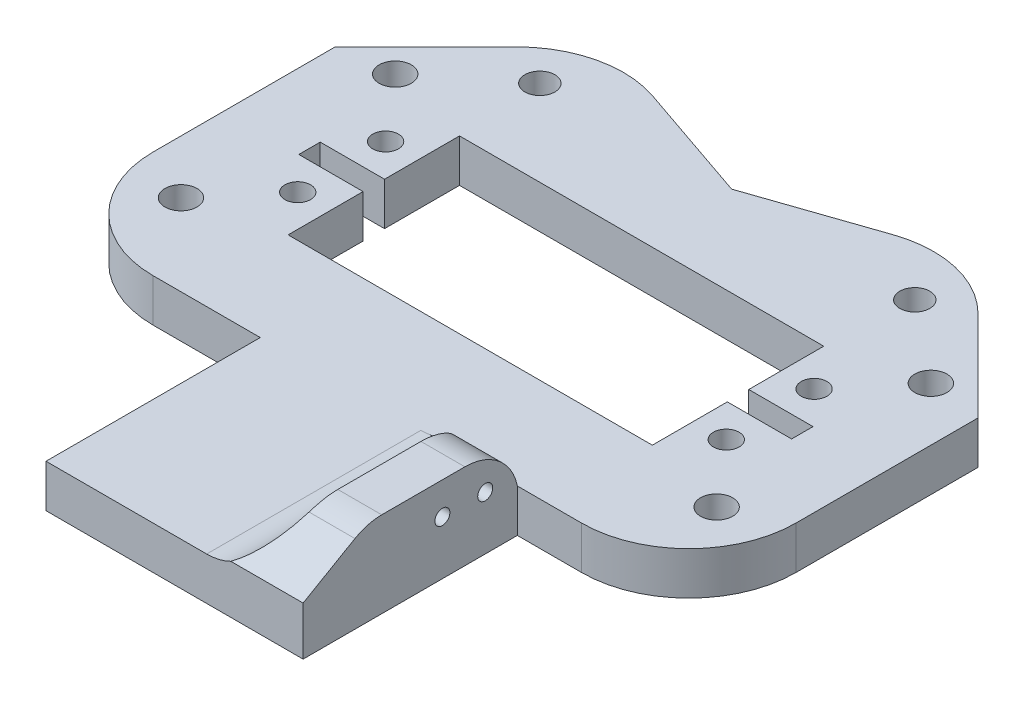
SolidWorks part; units mm, degrees
ref_plane "Front Plane" through (0, 0, 0) normal (0, 0, 1) x (1, 0, 0)
ref_plane "Top Plane" through (0, 0, 0) normal (0, 1, 0) x (1, 0, 0)
ref_plane "Right Plane" through (0, 0, 0) normal (1, 0, 0) x (0, 0, -1)
sketch "Sketch1" plane through (0, 0, 0) normal (0, 1, 0) x (1, 0, 0)
  line L0 (0, 0) -> (0, -43.9642) construction
  line L2 (-38.1, -12.7) -> (-38.1, 38.1)
  line L3 (-38.1, 38.1) -> (38.1, 38.1)
  line L4 (38.1, 38.1) -> (38.1, -12.7)
  line L7 (0, -43.9642) -> (0, 48.5365) construction
  line L8 (-19.05, -38.1) -> (19.05, -38.1)
  line L11 (-38.1, -12.7) -> (-19.05, -12.7)
  line L12 (-19.05, -38.1) -> (-19.05, -12.7)
  line L15 (38.1, -12.7) -> (19.05, -12.7)
  line L16 (19.05, -38.1) -> (19.05, -12.7)
  point P0 (0, 0)
  dimension "D1" = 76.2
  dimension "D2" = 50.8
  dimension "D3" = 38.1
  dimension "D4" = 76.2
extrude "Boss-Extrude1" add sketch "Sketch1" along normal blind 5.08
sketch "Sketch2" plane through (0, 5.08, 0) normal (0, 1, 0) x (1, 0, 0)
  line L0 (0, 44.8871) -> (0, -50.8249) construction
  line L2 (-19.05, -38.1) -> (19.05, -38.1) construction
  circle A0 centre (-22.225, 29.972) radius 1.778
  circle A1 centre (22.225, 29.972) radius 1.778
  dimension "D3" = 3.556
  dimension "D1" = 68.072
  dimension "D2" = 22.225
extrude "Cut-Extrude1" cut sketch "Sketch2" against normal through all
sketch "Sketch3" plane through (0, 5.08, 0) normal (0, 1, 0) x (1, 0, 0)
  line L0 (-38.1, 19.812) -> (38.1, 19.812) construction
  line L1 (-38.1, 38.1) -> (-38.1, -12.7) construction
  line L2 (38.1, -12.7) -> (38.1, 38.1) construction
  line L3 (38.1, 38.1) -> (-38.1, 38.1) construction
  line L4 (0, -43.0032) -> (0, 82.6272) construction
  line L6 (-21.59, -0.508) -> (21.59, -0.508)
  line L7 (-21.59, -0.508) -> (-21.59, 19.812)
  line L8 (-21.59, 19.812) -> (21.59, 19.812)
  line L9 (21.59, -0.508) -> (21.59, 19.812)
  line L10 (-21.59, -0.508) -> (21.59, 19.812) construction
  line L11 (-21.59, 19.812) -> (21.59, -0.508) construction
  point P8 (0, 9.652)
  point P12 (0, 19.812)
  dimension "D1" = 18.288
  dimension "D2" = 20.32
  dimension "D3" = 43.18
extrude "Cut-Extrude2" cut sketch "Sketch3" against normal through all
sketch "Sketch10" plane through (0, 0, 0) normal (0, -1, 0) x (1, 0, 0)
  line L0 (0, -77.724) -> (0, 38.1) construction
  line L1 (84.0119, -9.652) -> (-41.0442, -9.652) construction
  line L2 (-19.05, 38.1) -> (19.05, 38.1) construction
  line L5 (21.59, 0.508) -> (21.59, -19.812) construction
  circle A0 centre (25.4, -14.859) radius 1.524
  circle A1 centre (25.4, -4.445) radius 1.524
  circle A2 centre (-25.4, -14.859) radius 1.524
  circle A3 centre (-25.4, -4.445) radius 1.524
  point P3 (0, -19.812)
  point P8 (21.4838, -9.652)
  dimension "D3" = 3.048
  dimension "D1" = 5.207
  dimension "D2" = 3.81
extrude "Cut-Extrude3" cut sketch "Sketch10" against normal through all
sketch "Sketch11" plane through (0, 0, 0) normal (0, -1, 0) x (1, 0, 0)
  line L0 (21.59, -9.652) -> (-38.1, -9.652) construction
  line L1 (21.59, 0.508) -> (21.59, -19.812) construction
  line L2 (-38.1, -38.1) -> (-38.1, 12.7) construction
  line L3 (-38.1, -9.652) -> (41.0047, -9.652) construction
  line L4 (0, -19.812) -> (0, 0.508) construction
  line L5 (29.21, -8.382) -> (21.59, -8.382)
  line L6 (29.21, -8.382) -> (29.21, -10.922)
  line L7 (29.21, -10.922) -> (21.59, -10.922)
  line L8 (21.59, -8.382) -> (21.59, -10.922)
  line L9 (29.21, -8.382) -> (21.59, -10.922) construction
  line L10 (29.21, -10.922) -> (21.59, -8.382) construction
  line L11 (21.59, -19.812) -> (-21.59, -19.812) construction
  line L12 (-21.59, 0.508) -> (21.59, 0.508) construction
  line L13 (-29.21, -8.382) -> (-29.21, -10.922)
  line L14 (-29.21, -8.382) -> (-21.59, -8.382)
  line L15 (-29.21, -10.922) -> (-21.59, -10.922)
  line L16 (-21.59, -8.382) -> (-21.59, -10.922)
  point P6 (25.4, -9.652)
  dimension "D1" = 2.54
  dimension "D2" = 7.62
extrude "Cut-Extrude4" cut sketch "Sketch11" against normal through all
sketch "Sketch12" plane through (0, 0, 0) normal (0, -1, 0) x (1, 0, 0)
  line L0 (0, -51.1344) -> (0, 49.4945) construction
  line L1 (22.225, -8.8096) -> (22.225, -51.1344) construction
  line L2 (-22.225, -8.8096) -> (-22.225, -51.1344) construction
  line L3 (22.225, -38.1) -> (0, -30.48)
  line L4 (38.1, -38.1) -> (-38.1, -38.1) construction
  line L5 (0, -30.48) -> (-22.225, -38.1)
  line L6 (-22.225, -38.1) -> (22.225, -38.1)
  point P7 (22.225, -29.972)
  point P10 (-22.225, -29.972)
  dimension "D1" = 7.62
extrude "Cut-Extrude5" cut sketch "Sketch12" against normal through all
sketch "Sketch14" plane through (0, 0, 0) normal (0, -1, 0) x (1, 0, 0)
  line L0 (0, -30.48) -> (0, 38.1) construction
  line L1 (-19.05, 38.1) -> (19.05, 38.1) construction
  line L2 (29.21, -9.652) -> (-45.789, -9.652) construction
  line L3 (29.21, -10.922) -> (29.21, -8.382) construction
  line L4 (-45.789, -9.652) -> (38.9898, -9.652) construction
  line L5 (38.1, 12.7) -> (38.1, -38.1) construction
  circle A0 centre (31.75, 3.048) radius 1.905
  circle A1 centre (31.75, -22.352) radius 1.905
  circle A2 centre (-31.75, 3.048) radius 1.905
  circle A3 centre (-31.75, -22.352) radius 1.905
  dimension "D1" = 3.81
  dimension "D2" = 6.35
  dimension "D3" = 12.7
extrude "Cut-Extrude6" cut sketch "Sketch14" against normal through all
chamfer "Chamfer1" distance 16.51 angle 45 1 edges at (38.1, 2.54, -38.1)
chamfer "Chamfer3" distance 16.51 angle 45 1 edges at (-38.1, 2.54, -38.1)
fillet "Fillet1" radius 12.7 2 edges at (-21.7521, 2.54, -37.9379) (21.7521, 2.54, -37.9379)
fillet "Fillet2" radius 12.7 2 edges at (-38.1, 2.54, 12.7) (38.1, 2.54, 12.7)
sketch "Sketch15" plane through (0, 0, 0) normal (0, -1, 0) x (1, 0, 0)
  line L0 (-19.05, 38.1) -> (19.05, 38.1) construction
  line L1 (19.05, 12.7) -> (12.7, 12.7)
  line L2 (19.05, 12.7) -> (19.05, 38.1)
  line L3 (19.05, 38.1) -> (12.7, 38.1)
  line L4 (12.7, 12.7) -> (12.7, 38.1)
  line L6 (-19.05, 12.7) -> (-12.7, 12.7)
  line L7 (-19.05, 12.7) -> (-19.05, 38.1)
  line L8 (-19.05, 38.1) -> (-12.7, 38.1)
  line L9 (-12.7, 12.7) -> (-12.7, 38.1)
  dimension "D1" = 25.4
extrude "Cut-Extrude7" cut sketch "Sketch15" against normal through all
sketch "Sketch18" plane through (12.7, 0, 0) normal (1, 0, 0) x (0, 0, -1)
  line L1 (-12.7, 0) -> (-38.1, 0)
  line L2 (-12.7, 0) -> (-12.7, 12.7)
  line L3 (-12.7, 12.7) -> (-38.1, 12.7)
  line L4 (-38.1, 0) -> (-38.1, 12.7)
  dimension "D1" = 12.7
extrude "Boss-Extrude3" add sketch "Sketch18" along normal blind 5.08
sketch "Sketch19" plane through (17.78, 0, 0) normal (1, 0, 0) x (0, 0, -1)
  line L0 (-12.7, 12.7) -> (-38.1, 12.7) construction
  line L1 (-12.7, 0) -> (-25.4, 0) construction
  line L2 (-12.7, 0) -> (-12.7, 12.7) construction
  line L3 (-12.7, 12.7) -> (-25.4, 12.7) construction
  line L4 (-25.4, 0) -> (-25.4, 12.7) construction
  line L5 (-12.7, 6.35) -> (-25.4, 6.35) construction
  line L6 (-25.4, 6.35) -> (-19.05, 6.35) construction
  line L7 (-19.05, 6.35) -> (-19.05, 12.7) construction
  line L8 (-19.05, 12.7) -> (-19.05, 0) construction
  circle A0 centre (-16.51, 6.35) radius 0.889
  circle A1 centre (-21.59, 6.35) radius 0.889
  dimension "D1" = 1.778
  dimension "D2" = 5.08
extrude "Cut-Extrude9" cut sketch "Sketch19" against normal through all
fillet "Fillet4" radius 6.35 1 edges at (12.7, 5.08, 25.4)
sketch "Sketch20" plane through (17.78, 0, 0) normal (1, 0, 0) x (0, 0, -1)
  line L0 (-38.1, 12.7) -> (-38.1, 0) construction
  line L1 (-12.7, 12.7) -> (-38.1, 12.7)
  line L2 (-12.7, 12.7) -> (-12.7, 10.16)
  line L3 (-12.7, 10.16) -> (-38.1, 10.16)
  line L4 (-38.1, 12.7) -> (-38.1, 10.16)
  dimension "D1" = 2.54
extrude "Cut-Extrude10" cut sketch "Sketch20" against normal through all
chamfer "Chamfer4" distance 7.62 angle 30 1 edges at (15.1759, 10.16, 38.1) first distance on face at (15.1759, 10.16, 25.4)
fillet "Fillet5" radius 6.35 1 edges at (15.1759, 10.16, 30.48)
fillet "Fillet6" radius 6.35 1 edges at (15.1759, 10.16, 12.7)
